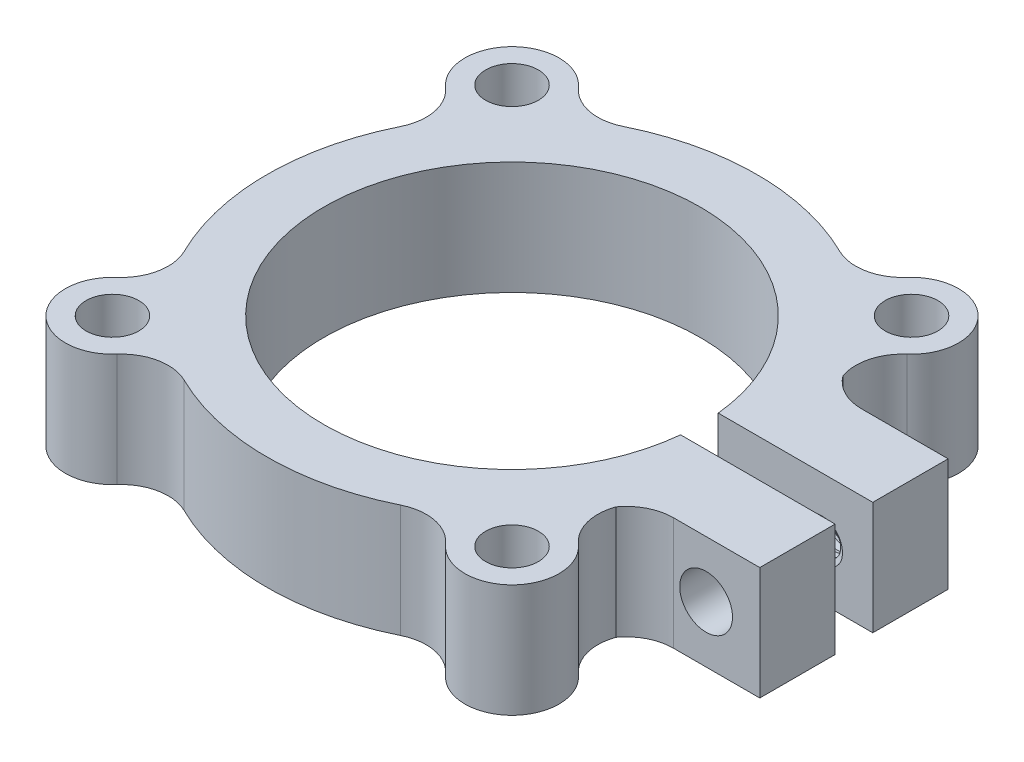
SolidWorks part; units mm, degrees
ref_plane "Front Plane" through (0, 0, 0) normal (0, 0, 1) x (1, 0, 0)
ref_plane "Top Plane" through (0, 0, 0) normal (0, 1, 0) x (1, 0, 0)
ref_plane "Right Plane" through (0, 0, 0) normal (1, 0, 0) x (0, 0, -1)
ref_plane "Plane1" through (0, 7.62, 0) normal (0, 1, 0) x (1, 0, 0)
sketch "Sketch1" plane through (0, 7.62, 0) normal (0, 1, 0) x (1, 0, 0)
  line L0 (23.058, -6.35) -> (23.058, 6.35)
  line L1 (23.058, 6.35) -> (17.2271, 6.35)
  line L2 (17.2271, -6.35) -> (23.058, -6.35)
  arc A0 (17.2271, 6.35) -> (14.6595, 7.6574) centre (17.2271, 9.525) cw
  arc A1 (14.6595, 7.6574) -> (15.5648, 11.0841) centre (17.6592, 8.6979) cw
  arc A2 (15.5648, 11.0841) -> (11.0841, 15.5648) centre (13.4704, 13.4704) ccw
  arc A3 (11.0841, 15.5648) -> (7.295, 14.8109) centre (8.6979, 17.6592) cw
  arc A4 (7.295, 14.8109) -> (-7.295, 14.8109) centre (0, 0) ccw
  arc A5 (-7.295, 14.8109) -> (-11.0841, 15.5648) centre (-8.6979, 17.6592) cw
  arc A6 (-11.0841, 15.5648) -> (-15.5648, 11.0841) centre (-13.4704, 13.4704) ccw
  arc A7 (-15.5648, 11.0841) -> (-14.8109, 7.295) centre (-17.6592, 8.6979) cw
  arc A8 (-14.8109, 7.295) -> (-14.8109, -7.295) centre (0, 0) ccw
  arc A9 (-14.8109, -7.295) -> (-15.5648, -11.0841) centre (-17.6592, -8.6979) cw
  arc A10 (-15.5648, -11.0841) -> (-11.0841, -15.5648) centre (-13.4704, -13.4704) ccw
  arc A11 (-11.0841, -15.5648) -> (-7.295, -14.8109) centre (-8.6979, -17.6592) cw
  arc A12 (-7.295, -14.8109) -> (7.295, -14.8109) centre (0, 0) ccw
  arc A13 (7.295, -14.8109) -> (11.0841, -15.5648) centre (8.6979, -17.6592) cw
  arc A14 (11.0841, -15.5648) -> (15.5648, -11.0841) centre (13.4704, -13.4704) ccw
  arc A15 (15.5648, -11.0841) -> (14.6595, -7.6574) centre (17.6592, -8.6979) cw
  arc A16 (14.6595, -7.6574) -> (17.2271, -6.35) centre (17.2271, -9.525) cw
extrude "Boss-Extrude1" add sketch "Sketch1" against normal blind 7.62
sketch "Sketch2" plane through (0, 0, 0) normal (0, -1, 0) x (1, 0, 0)
  line L0 (23.058, -1.27) -> (23.058, 1.27)
  line L1 (23.058, 1.27) -> (12.6363, 1.27)
  line L2 (12.6363, -1.27) -> (23.058, -1.27)
  arc A0 (12.6363, 1.27) -> (12.6363, -1.27) centre (0, 0) cw
extrude "Cut-Extrude1" cut sketch "Sketch2" against normal through all
sketch "Sketch3" plane through (0, 0, 0) normal (0, 0, 1) x (1, 0, 0)
  line L0 (12.7, 7.62) -> (0, 7.62)
  line L1 (0, 7.62) -> (0, 0)
  line L2 (0, 0) -> (12.7, 0)
  line L3 (12.7, 0) -> (12.7, 7.62)
  line L4 (0, 7.62) -> (0, 0) construction
revolve "Cut-Revolve1" cut sketch "Sketch3" angle 360 about L4 reverse direction yes
hole_wizard "#6 Clearance Hole1" positions "Sketch5" profile "Sketch4" hole size "#6" standard "ANSI Inch" end condition through all
sketch "Sketch5" plane through (0, 7.62, 0) normal (0, 1, 0) x (1, 0, 0)
  point P0 (13.4704, -13.4704)
  point P1 (-13.4704, -13.4704)
  point P2 (-13.4704, 13.4704)
  point P3 (13.4704, 13.4704)
sketch "Sketch4" plane through (13.4704, 7.62, 13.4704) normal (1, 0, 0) x (0, 0, 1)
  line L0 (0, 0) -> (0, 7.62)
  line L1 (0, 7.62) -> (1.778, 7.62)
  line L2 (1.778, 7.62) -> (1.778, 0)
  line L5 (1.778, 0) -> (0, 0)
  line L11 (0, -6.35) -> (0, 107.95) construction
  dimension "Thru Hole Dia." = 3.556
  dimension "Thru Hole Depth" = 7.62
hole_wizard "Tap Drill for #5-40 Tap1" positions "Sketch7" profile "Sketch6" hole size "#5-40" standard "ANSI Inch" end condition up to next
sketch "Sketch7" plane through (0, 0, -6.35) normal (0, 0, -1) x (-1, 0, 0)
  point P0 (-19.4388, 3.81)
sketch "Sketch6" plane through (19.4388, 3.81, -6.35) normal (1, 0, 0) x (0, 1, 0)
  line L0 (0, 0) -> (0, 5.08)
  line L1 (0, 5.08) -> (1.289, 5.08)
  line L2 (1.289, 5.08) -> (1.289, 0)
  line L5 (1.289, 0) -> (0, 0)
  line L11 (0, -6.35) -> (0, 107.95) construction
  dimension "Thru Hole Dia." = 2.5781
  dimension "Thru Hole Depth" = 5.08
hole_wizard "#5 Clearance Hole2" positions "Sketch9" profile "Sketch8" hole size "#5" standard "ANSI Inch" end condition up to next
sketch "Sketch9" plane through (0, 0, 6.35) normal (0, 0, 1) x (1, 0, 0)
  line L0 (17.2271, 0) -> (17.2271, 7.62) construction
  line L1 (17.2271, 7.62) -> (23.058, 7.62) construction
  point P0 (19.4388, 3.81)
  dimension "D1" = 2.2117
  dimension "D2" = 3.81
sketch "Sketch8" plane through (19.4388, 3.81, 6.35) normal (1, 0, 0) x (0, -1, 0)
  line L0 (0, 0) -> (0, 5.08)
  line L1 (0, 5.08) -> (1.778, 5.08)
  line L2 (1.778, 5.08) -> (1.778, 0)
  line L5 (1.778, 0) -> (0, 0)
  line L11 (0, -6.35) -> (0, 107.95) construction
  dimension "Thru Hole Dia." = 3.556
  dimension "Thru Hole Depth" = 5.08
thread "Thread2" pitch 0.635 method cut profile "Thread Profile2" start angle 0, offset 1.27, length 0, pitch 0.635, diameter 2.5781
ref_plane "Plane3" through (18.1497, 3.81, 0) normal (0, -1, 0) x (-1, 0, 0)
sketch "Thread Profile2" plane through (18.1497, 3.81, 0) normal (0, -1, 0) x (-1, 0, 0)
  line L0 (0, 0) -> (0, 0.635) construction
  line L1 (0, 0) -> (0.3437, 0.1984)
  line L2 (0.3437, 0.1984) -> (0.3437, 0.2778)
  line L3 (0.3437, 0.2778) -> (0, 0.4762)
  line L4 (0.3437, 0.2381) -> (0, 0.2381) construction
  line L11 (0, 0) -> (0, 0.4762)
  point P2 (0, 0)
  dimension "Pitch" = 0.635
  dimension "Profile_Angle" = 60
  dimension "Profile_Land" = 0.0794
  dimension "Profile_Height" = 0.3437
